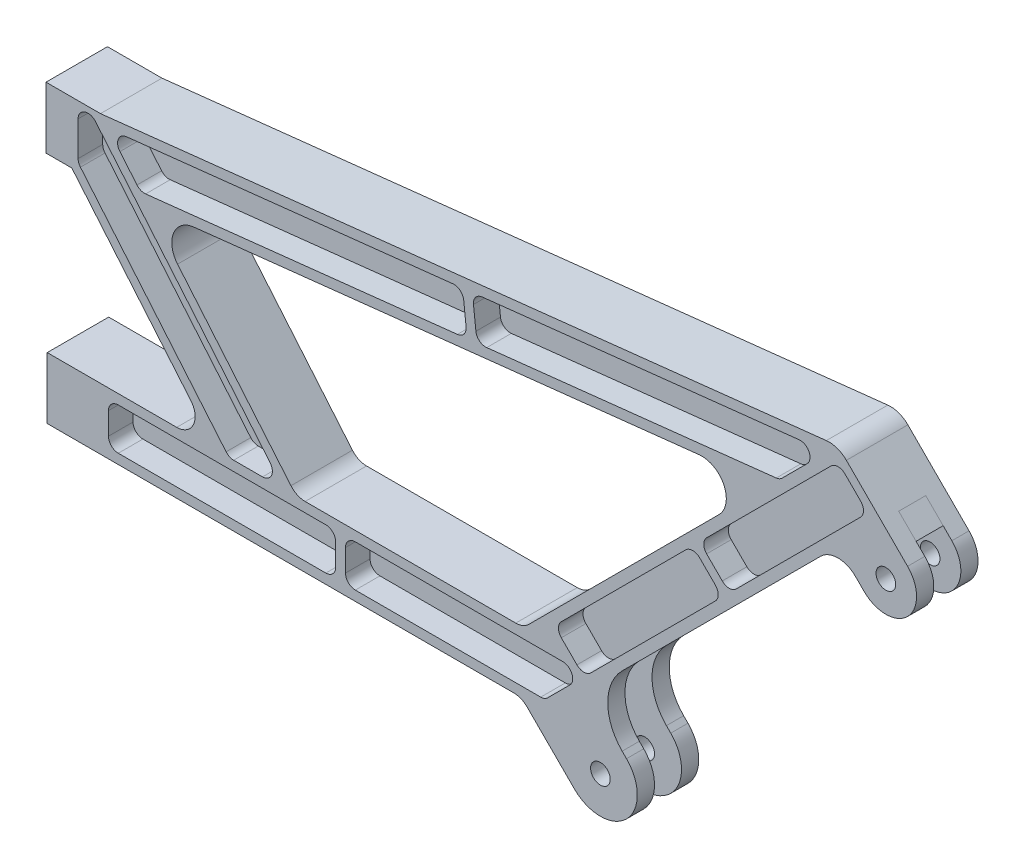
SolidWorks part; units mm, degrees
material "6061-T6 (SS)"
ref_plane "Front Plane" through (0, 0, 0) normal (0, 0, 1) x (1, 0, 0)
ref_plane "Top Plane" through (0, 0, 0) normal (0, 1, 0) x (1, 0, 0)
ref_plane "Right Plane" through (0, 0, 0) normal (1, 0, 0) x (0, 0, -1)
sketch "Sketch1" plane through (0, 0, 0) normal (0, 0, 1) x (1, 0, 0)
  line L0 (-241.9514, -88.161) -> (-288.0752, -33.1927)
  line L1 (-150.5152, -90.8401) -> (-236.206, -90.8401)
  line L2 (-67.8181, -11.2496) -> (-145.2119, -88.6434)
  line L3 (-16.0497, 33.7315) -> (8.8396, 8.8381)
  line L4 (-12.3744, -5.3033) -> (-8.8388, -8.8388)
  line L5 (-26.5165, -5.3033) -> (-107.2487, -86.0355)
  line L6 (-145.9582, -118.0368) -> (-126.6942, -137.3008)
  line L7 (-151.2615, -115.8401) -> (-341.1902, -115.8401)
  line L8 (-341.1902, -115.8401) -> (-341.0844, -90.8403)
  line L9 (-288.4221, -90.8403) -> (-341.0844, -90.8403)
  line L10 (-282.6768, -78.5194) -> (-331.0753, -20.8403)
  line L11 (-341.5776, -20.8403) -> (-331.0753, -20.8403)
  line L12 (-341.5776, -20.8403) -> (-341.5776, 4.1597)
  line L13 (-341.5776, 4.1597) -> (-319.4176, 4.1597)
  line L14 (-107.2487, -114.3198) -> (-105.481, -116.0876)
  line L15 (-319.4176, 4.1597) -> (-24.2138, 36.6012)
  line L16 (-281.5072, -16.8246) -> (-75.9816, 5.7616)
  arc A4 (8.8388, -8.8388) -> (8.8396, 8.8381) centre (0, 0) ccw
  arc A5 (-8.8388, -8.8388) -> (8.8388, -8.8388) centre (0, 0) ccw
  arc A6 (-12.3744, -5.3033) -> (-26.5165, -5.3033) centre (-19.4454, -12.3744) ccw
  arc A7 (-107.2487, -86.0355) -> (-107.2487, -114.3198) centre (-93.1066, -100.1777) ccw
  arc A8 (-105.481, -137.3008) -> (-105.481, -116.0876) centre (-116.0876, -126.6942) ccw
  arc A9 (-126.6942, -137.3008) -> (-105.481, -137.3008) centre (-116.0876, -126.6942) ccw
  circle A12 centre (-116.0876, -126.6942) radius 4
  circle A13 centre (0, 0) radius 4
  arc A15 (-151.2615, -115.8401) -> (-145.9582, -118.0368) centre (-151.2615, -123.3401) cw
  arc A16 (-150.5152, -90.8401) -> (-145.2119, -88.6434) centre (-150.5152, -83.3401) ccw
  arc A17 (-236.206, -90.8401) -> (-241.9514, -88.161) centre (-236.206, -83.3401) cw
  arc A18 (-288.4221, -90.8403) -> (-282.6768, -78.5194) centre (-288.4221, -83.3403) ccw
  arc A19 (-288.0752, -33.1927) -> (-281.5072, -16.8246) centre (-280.4148, -26.7648) cw
  arc A20 (-67.8181, -11.2496) -> (-75.9816, 5.7616) centre (-74.8892, -4.1785) ccw
  arc A21 (-16.0497, 33.7315) -> (-24.2138, 36.6012) centre (-23.1214, 26.661) ccw
  dimension "D2" = 25
  dimension "D3" = 25
  dimension "D7" = 25
  dimension "D9" = 10
  dimension "D1" = 25
  dimension "D4" = 25
  dimension "D5" = 130
  dimension "D6" = 25
  dimension "D8" = 119.9998
extrude "Boss-Extrude1" add sketch "Sketch1" along normal blind 25
sketch "Sketch2" plane through (0, 0, 25) normal (0, 0, 1) x (1, 0, 0)
  line L0 (-107.2487, -86.0355) -> (-26.5165, -5.3033) construction
  line L1 (-137.5386, -110.6685) -> (-128.5386, -101.6685)
  line L2 (-131.367, -94.8401) -> (-215.77, -94.8401)
  line L3 (-67.8181, -11.2496) -> (-145.2119, -88.6434) construction
  line L4 (-107.2487, -86.0355) -> (-26.5165, -5.3033)
  line L5 (-67.8181, -11.2496) -> (-145.2119, -88.6434)
  line L6 (-22.272, 28.6397) -> (-72.893, -21.9813)
  line L7 (-119.9767, -93.1066) -> (-69.3575, -42.4874)
  line L8 (-131.9975, -86.7426) -> (-125.6335, -93.1066)
  line L9 (-10.2515, 22.275) -> (-16.6149, 28.6394)
  line L10 (-64.9897, -14.078) -> (-142.3835, -91.4718) construction
  line L11 (-110.0772, -83.2071) -> (-29.3449, -2.4749) construction
  line L12 (-341.1902, -115.8401) -> (-151.2615, -115.8401) construction
  line L13 (-341.1902, -115.8401) -> (-151.2615, -115.8401)
  line L14 (-312.1731, -111.8401) -> (-227.77, -111.8401)
  line L15 (-341.1902, -111.8401) -> (-151.2615, -111.8401) construction
  line L16 (-341.0844, -90.8403) -> (-341.1902, -115.8401) construction
  line L17 (-316.1731, -98.8401) -> (-316.1731, -107.8401)
  line L18 (-150.5152, -90.8401) -> (-236.206, -90.8401) construction
  line L19 (8.8396, 8.8381) -> (-16.0497, 33.7315) construction
  line L20 (-145.9582, -118.0368) -> (-126.6942, -137.3008) construction
  line L21 (-65.1149, -38.2448) -> (-77.1357, -26.224) construction
  line L22 (-72.893, -27.6382) -> (-66.5291, -34.0022)
  line L23 (-75.7215, -30.4666) -> (-69.3575, -36.8306)
  line L24 (-81.3783, -30.4666) -> (-131.9975, -81.0858)
  line L25 (-60.8722, -34.0022) -> (-10.2517, 16.6183)
  line L26 (-221.77, -94.8401) -> (-221.77, -111.8401) construction
  line L27 (-219.77, -98.8401) -> (-219.77, -107.8401)
  line L28 (-223.77, -98.8401) -> (-223.77, -107.8401)
  line L29 (-215.77, -111.8401) -> (-140.367, -111.8401)
  line L30 (-227.77, -94.8401) -> (-312.1731, -94.8401)
  line L31 (-328.5079, -16.2212) -> (-328.5079, -2.2197)
  line L32 (-253.5029, -90.8401) -> (-265.2515, -90.8402)
  line L33 (-321.4437, 0.3514) -> (-250.4387, -84.269)
  line L34 (-241.9514, -88.161) -> (-288.0752, -33.1927) construction
  line L35 (-327.5721, -18.7924) -> (-268.3157, -89.4113)
  line L36 (-331.0753, -20.8403) -> (-282.6768, -78.5194) construction
  line L37 (-341.5776, 4.1597) -> (-341.5776, -20.8403) construction
  line L38 (-308.8907, 1.2925) -> (-176.1091, 15.8845)
  line L39 (-24.2138, 36.6012) -> (-319.4176, 4.1597) construction
  line L40 (-301.0609, -14.9494) -> (-174.2521, -1.0137)
  line L41 (-75.9816, 5.7616) -> (-281.5072, -16.8246) construction
  line L42 (-311.5179, -5.2547) -> (-304.562, -13.5445)
  line L43 (-32.0118, 24.5568) -> (-42.1838, 14.3847)
  line L44 (-170.145, 16.5399) -> (-168.288, -0.3583) construction
  line L45 (-171.6961, 12.3454) -> (-170.713, 3.3993)
  line L46 (-167.7201, 12.7824) -> (-166.7369, 3.8362)
  line L47 (-164.181, 17.1954) -> (-35.2771, 31.3613)
  line L48 (-162.3239, 0.2971) -> (-44.5753, 13.2371)
  arc A0 (-22.272, 28.6397) -> (-16.6149, 28.6394) centre (-19.4436, 25.8113) cw
  arc A1 (-10.2517, 16.6183) -> (-10.2515, 22.275) centre (-13.0801, 19.4468) ccw
  arc A2 (-119.9767, -93.1066) -> (-125.6335, -93.1066) centre (-122.8051, -90.2782) cw
  arc A3 (-131.9975, -81.0858) -> (-131.9975, -86.7426) centre (-129.169, -83.9142) ccw
  arc A4 (-312.1731, -111.8401) -> (-316.1731, -107.8401) centre (-312.1731, -107.8401) cw
  arc A5 (-312.1731, -94.8401) -> (-316.1731, -98.8401) centre (-312.1731, -98.8401) ccw
  arc A6 (-140.367, -111.8401) -> (-137.5386, -110.6685) centre (-140.367, -107.8401) ccw
  arc A7 (-128.5386, -101.6685) -> (-131.367, -94.8401) centre (-131.367, -98.8401) ccw
  arc A8 (-75.7215, -30.4666) -> (-81.3783, -30.4666) centre (-78.5499, -33.295) ccw
  arc A9 (-69.3575, -36.8306) -> (-69.3575, -42.4874) centre (-72.1859, -39.659) cw
  arc A10 (-66.5291, -34.0022) -> (-60.8722, -34.0022) centre (-63.7006, -31.1737) ccw
  arc A11 (-72.893, -27.6382) -> (-72.893, -21.9813) centre (-70.0646, -24.8098) cw
  arc A12 (-223.77, -107.8401) -> (-227.77, -111.8401) centre (-227.77, -107.8401) cw
  arc A13 (-219.77, -107.8401) -> (-215.77, -111.8401) centre (-215.77, -107.8401) ccw
  arc A14 (-219.77, -98.8401) -> (-215.77, -94.8401) centre (-215.77, -98.8401) cw
  arc A15 (-223.77, -98.8401) -> (-227.77, -94.8401) centre (-227.77, -98.8401) ccw
  arc A16 (-250.4387, -84.269) -> (-253.5029, -90.8401) centre (-253.5029, -86.8401) cw
  arc A17 (-268.3157, -89.4113) -> (-265.2515, -90.8402) centre (-265.2515, -86.8402) ccw
  arc A18 (-327.5721, -18.7924) -> (-328.5079, -16.2212) centre (-324.5079, -16.2212) cw
  arc A19 (-321.4437, 0.3514) -> (-328.5079, -2.2197) centre (-324.5079, -2.2197) ccw
  arc A20 (-44.5753, 13.2371) -> (-42.1838, 14.3847) centre (-45.0122, 17.2132) ccw
  arc A21 (-35.2771, 31.3613) -> (-32.0118, 24.5568) centre (-34.8402, 27.3852) cw
  arc A22 (-166.7369, 3.8362) -> (-162.3239, 0.2971) centre (-162.7609, 4.2732) ccw
  arc A23 (-167.7201, 12.7824) -> (-164.181, 17.1954) centre (-163.744, 13.2193) cw
  arc A24 (-170.713, 3.3993) -> (-174.2521, -1.0137) centre (-174.6891, 2.9623) cw
  arc A25 (-171.6961, 12.3454) -> (-176.1091, 15.8845) centre (-175.6722, 11.9085) ccw
  arc A26 (-301.0609, -14.9494) -> (-304.562, -13.5445) centre (-301.4978, -10.9733) cw
  arc A27 (-308.8907, 1.2925) -> (-311.5179, -5.2547) centre (-308.4538, -2.6836) ccw
  point P34 (-316.1731, -111.8401)
  point P53 (-78.5499, -27.6382)
  point P58 (-63.7006, -36.8306)
  point P69 (-223.77, -111.8401)
  point P72 (-219.77, -111.8401)
  point P75 (-219.77, -94.8401)
  point P78 (-223.77, -94.8401)
  point P117 (-166.3, -0.1398)
  point P120 (-168.157, 16.7584)
  point P123 (-170.276, -0.5768)
  point P126 (-172.1331, 16.3215)
  dimension "D2" = 4
  dimension "D6" = 4
  dimension "D11" = 4
  dimension "D13" = 4
  dimension "D16" = 4
  dimension "D22" = 4
  dimension "D4" = 25
  dimension "D5" = 4
  dimension "D7" = 4
  dimension "D8" = 4
  dimension "D9" = 32
  dimension "D10" = 2
  dimension "D12" = 2
  dimension "D14" = 4
  dimension "D15" = 4
  dimension "D17" = 4
  dimension "D18" = 4
  dimension "D19" = 4
  dimension "D20" = 4
  dimension "D21" = 2
  dimension "D1" = 4
  dimension "D3" = 4
extrude "Cut-Extrude1" cut sketch "Sketch2" against normal blind 10 contours L33 A19 L31 A18 L35 A17 L32 A16 | L28 A15 L30 A5 L17 A4 L14 A12 | A14 L27 A13 L29 A6 L1 A7 L2 | A9 L23 A8 L24 A3 L8 A2 L7 | A11 L22 A10 L25 A1 L9 A0 L6 | A26 L40 A24 L45 A25 L38 A27 L42 | L43 A20 L48 A22 L46 A23 L47 A21 region at (-175.3079, -103.1533, 25) region at (-41.5723, -2.6814, 25) region at (-100.6775, -61.7866, 25) region at (-269.9715, -103.3401, 25) region at (-291.9066, -47.6042, 25)
ref_plane "Plane1" through (0, 0, 12.5) normal (0, 0, 1) x (1, 0, 0)
mirror "Mirror1" about plane through (0, 0, 12.5) normal (0, 0, 1) of "Cut-Extrude1"
sketch "Sketch3" plane through (0, 0, 12.5) normal (0, 0, 1) x (1, 0, 0)
  line L0 (-151.2615, -115.8401) -> (-141.1954, -115.8401)
  line L1 (-98.969, -77.7558) -> (-134.1243, -112.9111)
  line L2 (-107.2487, -86.0355) -> (-26.5165, -5.3033) construction
  line L3 (-151.2615, -115.8401) -> (-116.5971, -149.2186)
  line L4 (-116.5971, -149.2186) -> (-66.3597, -110.0186)
  line L5 (-66.3597, -110.0186) -> (-98.969, -77.7558)
  line L6 (-29.0156, -7.8024) -> (7.8698, 29.083)
  line L7 (7.8698, 29.083) -> (26.3533, -15.3879)
  line L8 (26.3533, -15.3879) -> (-12.041, -17.819)
  line L9 (-12.041, -17.819) -> (-29.0156, -7.8024)
  arc A0 (-134.1243, -112.9111) -> (-141.1954, -115.8401) centre (-141.1954, -105.8401) cw
  dimension "D1" = 10
extrude "Cut-Extrude2" cut sketch "Sketch3" against normal blind 5.5 and the other way blind 5.5
sketch "Sketch4" plane through (-10.6066, 10.6066, 0) normal (0.7071, -0.7071, 0) x (0, 0, -1)
  line L1 (-18, 12.5012) -> (-7, 12.5012)
  line L2 (-18, 12.5012) -> (-18, -12.5)
  line L3 (-18, -12.5) -> (-7, -12.5)
  line L4 (-7, 12.5012) -> (-7, -12.5)
extrude "Boss-Extrude2" add sketch "Sketch4" along normal blind 10
